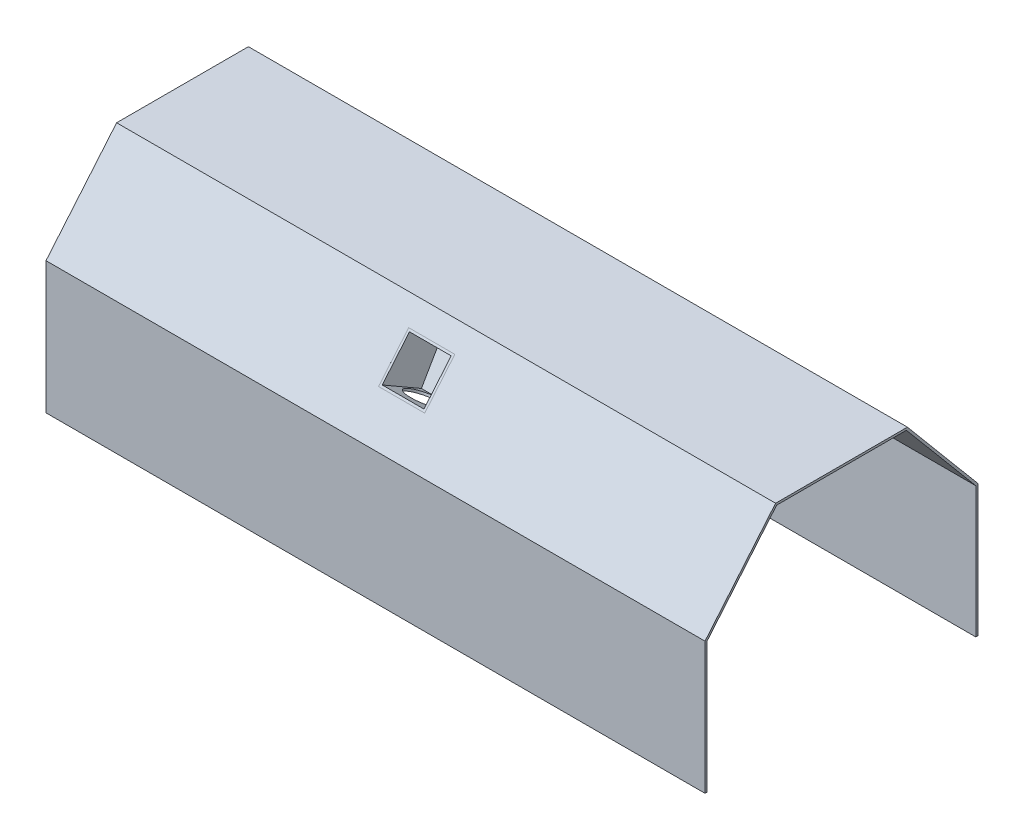
SolidWorks part; units mm, degrees
ref_plane "前视基准面" through (0, 0, 0) normal (0, 0, 1) x (1, 0, 0)
ref_plane "上视基准面" through (0, 0, 0) normal (0, 1, 0) x (1, 0, 0)
ref_plane "右视基准面" through (0, 0, 0) normal (1, 0, 0) x (0, 0, -1)
sketch "草图1" plane through (0, 0, 0) normal (0, 0, 1) x (1, 0, 0)
  line L0 (-150, 0) -> (150, 0)
  line L1 (150, 0) -> (150, 60)
  line L2 (150, 60) -> (-150, 60)
  line L3 (-150, 60) -> (-150, 0)
  point P4 (0, 0)
  dimension "D1" = 60
  dimension "D2" = 300
extrude "凸台-拉伸1" add sketch "草图1" against normal blind 1
ref_plane "基准面1" through (0, 35.2094, -29.5442) normal (0, 0.766, -0.6428) x (-1, 0, 0)
sketch "草图4" plane through (0, 35.2094, -29.5442) normal (0, 0.766, -0.6428) x (-1, 0, 0)
  line L0 (-150, 38.5673) -> (-150, 37.5643)
  line L1 (-150, 37.5643) -> (150, 37.5643)
  line L2 (150, 37.5643) -> (150, 38.5673)
  line L3 (150, 38.5673) -> (-150, 38.5673)
  dimension "D1" = 1.0029
extrude "凸台-拉伸2" add sketch "草图4" along normal blind 50
ref_plane "基准面2" through (0, 0, -32.1394) normal (0, 0, -1) x (-1, 0, 0)
sketch "草图5" plane through (0, 0, -32.1394) normal (0, 0, -1) x (-1, 0, 0)
  line L3 (150, 98.3022) -> (-150, 98.3022)
  line L4 (-150, 98.3022) -> (-150, 97.3008)
  line L5 (-150, 97.6576) -> (-150, 59.6315) construction
  line L6 (-150, 97.3008) -> (150, 97.3008)
  line L7 (150, 97.6576) -> (150, 59.6315) construction
  line L8 (150, 97.3008) -> (150, 98.3022)
  dimension "D1" = 1.0014
extrude "凸台-拉伸3" add sketch "草图5" along normal blind 60
sketch "草图6" plane through (0, 98.3022, 0) normal (0, 1, 0) x (1, 0, 0)
  line L0 (-150, 92.1394) -> (-150, 32.1394) construction
  line L1 (-150, 62.1394) -> (150, 62.1394)
  line L2 (150, 92.1394) -> (150, 32.1394) construction
ref_plane "基准面3" through (0, 0, -62.1394) normal (0, 0, 1) x (1, 0, 0)
mirror "镜向1" about plane through (0, 0, -62.1394) normal (0, 0, 1) of "凸台-拉伸2"
mirror "镜向2" about plane through (0, 0, -62.1394) normal (0, 0, 1) of "凸台-拉伸1"
ref_plane "基准面5" through (0, 15, 25.9808) normal (0, 0.5, 0.866) x (-1, 0, 0)
sketch "草图11" plane through (0, 15, 25.9808) normal (0, 0.5, 0.866) x (-1, 0, 0)
  line L0 (0, -14.9004) -> (0, -98.112) construction
  line L4 (-10.5, -70.2019) -> (-10.5, -91.2019)
  line L5 (-10.5, -91.2019) -> (10.5, -91.2019)
  line L6 (10.5, -91.2019) -> (10.5, -70.2019)
  line L7 (10.5, -70.2019) -> (-10.5, -70.2019)
  line L9 (150, -101.2019) -> (-150, -101.2019) construction
  point P14 (0, -70.2019)
  dimension "D1" = 21
  dimension "D2" = 21
  dimension "D3" = 10
extrude "凸台-拉伸5" add sketch "草图11" against normal blind 25
shell "抽壳1" thickness 1 removed face at (0, 84.8899, -14.3702) removed face at (0, 92.2534, -22.6163) removed face at (-10.5, 83.623, -16.5646) removed face at (10.5, 83.623, -16.5646) removed face at (0, 74.9926, -10.5129)
sketch "草图12" plane through (0, 60.7966, -35.101) normal (0, -0.866, 0.5) x (1, 0, 0)
  line L0 (0, 40.693) -> (0, 0) construction
  line L2 (-10.5, 5) -> (10.5, 5) construction
  circle A0 centre (0, 14) radius 8.5
  point P5 (0, 13.9356)
  dimension "D1" = 17
  dimension "D2" = 9
extrude "切除-拉伸4" cut sketch "草图12" against normal blind 1
